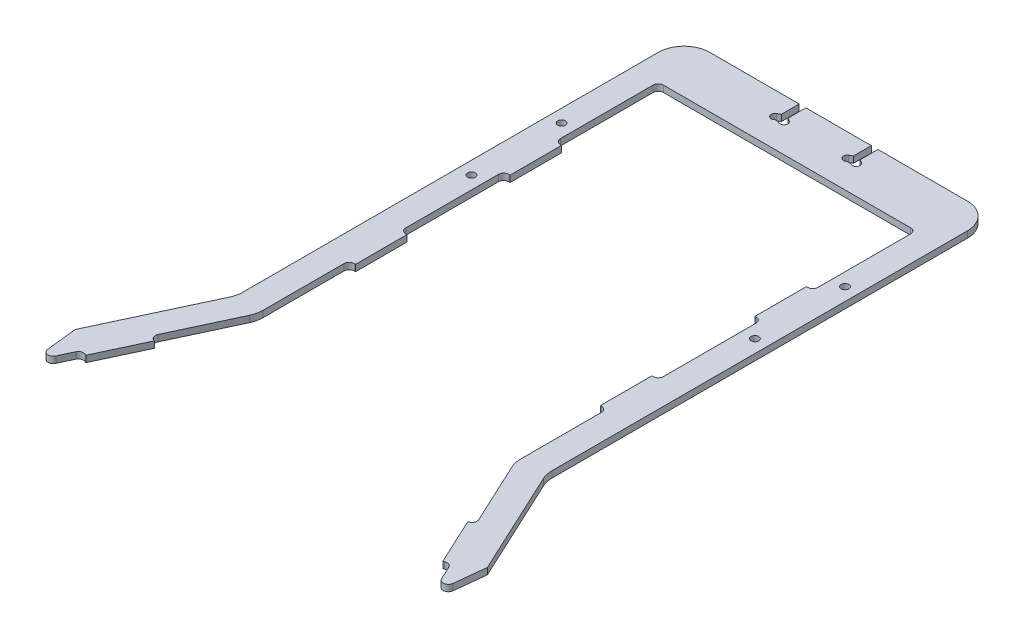
SolidWorks part; units mm, degrees
material "6061-T6 (SS)"
ref_plane "Front Plane" through (0, 0, 0) normal (0, 0, 1) x (1, 0, 0)
ref_plane "Top Plane" through (0, 0, 0) normal (0, 1, 0) x (1, 0, 0)
ref_plane "Right Plane" through (0, 0, 0) normal (1, 0, 0) x (0, 0, -1)
sketch "Sketch1" plane through (0, 0, 0) normal (0, 1, 0) x (1, 0, 0)
  line L0 (-76.2, 0) -> (76.2, 0)
  line L1 (-76.2, 0) -> (-76.2, -220.2788)
  line L3 (-63.5, -223.0943) -> (-63.5, -25.4)
  line L4 (-63.5, -25.4) -> (63.5, -25.4)
  line L5 (63.5, -25.4) -> (63.5, -223.0943)
  line L7 (76.2, -220.2788) -> (76.2, 0)
  line L8 (-76.2, -220.2788) -> (-113.1101, -299.4327)
  line L9 (-113.1101, -299.4327) -> (-101.6, -304.8)
  line L10 (-101.6, -304.8) -> (-63.5, -223.0943)
  line L11 (63.5, -223.0943) -> (101.6, -304.8)
  line L12 (76.2, -220.2788) -> (113.1101, -299.4327)
  line L13 (113.1101, -299.4327) -> (101.6, -304.8)
  point P4 (0, 0)
  dimension "D1" = 127
  dimension "D3" = 25.4
  dimension "D5" = 12.7
  dimension "D6" = 12.7
  dimension "D8" = 12.7
  dimension "D9" = 38.1
  dimension "D10" = 279.4
  dimension "D12" = 25
base flange "Base-Flange1" sketch "Sketch1" thickness 3.175 reverse thickness direction no parameters "D1"=3.175
sketch "Sketch7" plane through (0, 0, 0) normal (0, 1, 0) x (1, 0, 0)
  line L0 (-19.431, 0) -> (-19.431, -12.7)
  line L1 (76.2, 0) -> (-76.2, 0) construction
  line L2 (-19.431, -12.7) -> (-16.129, -12.7)
  line L3 (-16.129, -12.7) -> (-16.129, 0)
  line L4 (-16.129, 0) -> (-19.431, 0)
  line L9 (0, 0) -> (0, -25.4) construction
  line L10 (-63.5, -25.4) -> (63.5, -25.4) construction
  line L11 (16.129, 0) -> (19.431, 0)
  line L14 (16.129, -12.7) -> (16.129, 0)
  line L16 (19.431, -12.7) -> (16.129, -12.7)
  line L17 (19.431, 0) -> (19.431, -12.7)
  dimension "D1" = 12.7
  dimension "D2" = 3.302
  dimension "D3" = 32.258
extrude "Cut-Extrude1" cut sketch "Sketch7" against normal through all normal cut yes
sketch "Sketch12" plane through (0, 0, 0) normal (0, 1, 0) x (1, 0, 0)
  line L0 (-63.5, -223.0943) -> (-63.5, -25.4) construction
  line L1 (-63.5, -76.2) -> (-60.325, -76.2)
  line L2 (-63.5, -76.2) -> (-63.5, -101.6)
  line L3 (-63.5, -101.6) -> (-60.325, -101.6)
  line L4 (-60.325, -76.2) -> (-60.325, -101.6)
  line L5 (-80.131, -258.7596) -> (-90.8655, -281.7798)
  line L6 (-63.5, -152.4) -> (-60.325, -152.4)
  line L7 (-63.5, -152.4) -> (-63.5, -177.8)
  line L8 (-63.5, -177.8) -> (-60.325, -177.8)
  line L9 (-60.325, -152.4) -> (-60.325, -177.8)
  line L10 (-80.131, -258.7596) -> (-77.2535, -260.1014)
  line L11 (-90.8655, -281.7798) -> (-87.988, -283.1216)
  line L12 (-77.2535, -260.1014) -> (-87.988, -283.1216)
  line L13 (-101.6, -304.8) -> (-63.5, -223.0943) construction
  line L18 (-113.1101, -299.4327) -> (-101.6, -304.8) construction
  line L19 (0, 0) -> (0, -305.8108) construction
  line L24 (-63.5, -25.4) -> (63.5, -25.4) construction
  line L25 (77.2535, -260.1014) -> (87.988, -283.1216)
  line L26 (90.8655, -281.7798) -> (87.988, -283.1216)
  line L27 (80.131, -258.7596) -> (77.2535, -260.1014)
  line L28 (60.325, -152.4) -> (60.325, -177.8)
  line L29 (63.5, -177.8) -> (60.325, -177.8)
  line L30 (63.5, -152.4) -> (63.5, -177.8)
  line L31 (63.5, -152.4) -> (60.325, -152.4)
  line L32 (80.131, -258.7596) -> (90.8655, -281.7798)
  line L33 (60.325, -76.2) -> (60.325, -101.6)
  line L34 (63.5, -101.6) -> (60.325, -101.6)
  line L35 (63.5, -76.2) -> (63.5, -101.6)
  line L36 (63.5, -76.2) -> (60.325, -76.2)
  dimension "D1" = 25.4
  dimension "D2" = 3.175
  dimension "D3" = 50.8
  dimension "D4" = 50.8
  dimension "D5" = 25.4
base flange "Tab1" sketch "Sketch12" thickness 3.175 reverse thickness direction no parameters "D1"=3.175
sketch "Sketch13" plane through (0, 0, 0) normal (0, 1, 0) x (1, 0, 0)
  line L1 (-101.6, -304.8) -> (-98.9164, -299.0449)
  line L2 (-98.9164, -299.0449) -> (-101.6, -274.7492)
  line L4 (-76.2, -220.2788) -> (-113.1101, -299.4327) construction
  line L5 (-101.6, -274.7492) -> (-113.1101, -299.4327)
  line L10 (0, 0) -> (0, -299.0449) construction
  line L12 (101.6, -304.8) -> (98.9164, -299.0449)
  line L13 (113.1101, -299.4327) -> (101.6, -304.8)
  line L15 (101.6, -274.7492) -> (113.1101, -299.4327)
  line L16 (98.9164, -299.0449) -> (101.6, -274.7492)
  line L18 (-113.1101, -299.4327) -> (-101.6, -304.8)
  line L23 (-96.2327, -293.2899) -> (-101.6, -304.8) construction
  line L24 (-101.6, -304.8) -> (-90.8655, -281.7798) construction
  dimension "D1" = 24.2957
extrude "Cut-Extrude2" cut sketch "Sketch13" against normal through all normal cut yes
fillet "Fillet1" radius 2.54 14 edges at (-63.5, -1.5875, 25.4) (63.5, -1.5875, 25.4) (63.5, -1.5875, 177.8) (63.5, -1.5875, 152.4) (90.8655, -1.5875, 281.7798) (80.131, -1.5875, 258.7596) (-80.131, -1.5875, 258.7596) (-90.8655, -1.5875, 281.7798) (-63.5, -1.5875, 177.8) (-63.5, -1.5875, 152.4) (-63.5, -1.5875, 101.6) (-63.5, -1.5875, 76.2) (63.5, -1.5875, 76.2) (63.5, -1.5875, 101.6)
sketch "Sketch14" plane through (0, 0, 0) normal (0, 1, 0) x (1, 0, 0)
  line L0 (-19.431, -12.7) -> (-16.129, -12.7) construction
  line L1 (-19.431, -9.4871) -> (-18.669, -12.7) construction
  line L2 (-19.431, 0) -> (-19.431, -12.7) construction
  line L3 (-17.78, -12.7) -> (-17.78, -11.1209) construction
  line L4 (0, 0) -> (0, -4.4375) construction
  line L5 (-20.9272, -9.6631) -> (-19.431, -8.7993)
  line L6 (-19.431, -8.7993) -> (-19.431, -9.4871)
  line L7 (-16.129, -8.7993) -> (-16.129, -9.4871)
  line L8 (-14.6328, -9.6631) -> (-16.129, -8.7993)
  line L9 (19.431, -8.7993) -> (19.431, -9.4871)
  line L10 (20.9272, -9.6631) -> (19.431, -8.7993)
  line L11 (14.6328, -9.6631) -> (16.129, -8.7993)
  line L12 (16.129, -8.7993) -> (16.129, -9.4871)
  arc A0 (-20.9272, -9.6631) -> (-19.431, -9.4871) centre (-19.9747, -11.3129) ccw
  arc A5 (-14.6328, -9.6631) -> (-16.129, -9.4871) centre (-15.5853, -11.3129) cw
  arc A6 (20.9272, -9.6631) -> (19.431, -9.4871) centre (19.9747, -11.3129) cw
  arc A7 (14.6328, -9.6631) -> (16.129, -9.4871) centre (15.5853, -11.3129) ccw
  dimension "D1" = 3.81
  dimension "D2" = 3.302
  dimension "D3" = 0.762
  dimension "D4" = 30
extrude "Cut-Extrude3" cut sketch "Sketch14" against normal through all normal cut yes
fillet "Fillet2" radius 12.7 6 edges at (-76.2, -1.5875, 220.2788) (76.2, -1.5875, 220.2788) (76.2, -1.5875, 0) (-76.2, -1.5875, 0) (63.5, -1.5875, 223.0943) (-63.5, -1.5875, 223.0943)
fillet "Fillet3" radius 2.54 2 edges at (98.9164, -1.5875, 299.0449) (-98.9164, -1.5875, 299.0449)
sketch "Sketch17" plane through (0, 0, 0) normal (0, 1, 0) x (1, 0, 0)
  line L0 (63.5, -66.675) -> (76.2, -66.675) construction
  line L1 (63.5, -27.94) -> (63.5, -73.66) construction
  line L2 (76.2, -217.4632) -> (76.2, -12.7) construction
  line L4 (-60.96, -25.4) -> (60.96, -25.4) construction
  line L5 (0, 0) -> (0, 30.5399) construction
  point P0 (69.85, -66.675)
  point P2 (69.85, -111.125)
  point P27 (-69.85, -111.125)
  point P28 (-69.85, -66.675)
  dimension "D1" = 44.45
  dimension "D2" = 41.275
hole_wizard "#6 Clearance Hole1" positions "Sketch17" profile "Sketch16" hole size "#6" standard "ANSI Inch" end condition up to next
sketch "Sketch16" plane through (69.85, 0, 66.675) normal (1, 0, 0) x (0, 0, 1)
  line L0 (0, 0) -> (0, 3.175)
  line L1 (0, 3.175) -> (1.8986, 3.175)
  line L2 (1.8986, 3.175) -> (1.8986, 0)
  line L5 (1.8986, 0) -> (0, 0)
  line L11 (0, -6.35) -> (0, 107.95) construction
  dimension "Thru Hole Dia." = 3.7973
  dimension "Thru Hole Depth" = 3.175
sketch "Bend-Lines1" [suppressed] plane through (0, 0, 0) normal (0, 1, 0) x (1, 0, 0)
sketch "Bounding-Box1" [suppressed] plane through (0, 0, 0) normal (0, 1, 0) x (1, 0, 0)
sheet metal parameters "Sheet-Metal1" thickness 3.175 parameters "D1"=3.175
flat pattern "Flat-Pattern1" [suppressed]
sketch "Bend-Lines2" plane through (0, 0, 0) normal (0, 1, 0) x (1, 0, 0)
sketch3d "Bounding-Box2" [suppressed]
  line L0 (-150.221, -355.6, 0) -> (-150.221, 0, 0) construction
  line L1 (150.221, -355.6, 0) -> (150.221, 0, 0) construction
  line L2 (-150.221, -355.6, 0) -> (150.221, -355.6, 0) construction
  line L3 (-150.221, 0, 0) -> (150.221, 0, 0) construction
sheet metal parameters "Sheet-Metal2" thickness 3.175 parameters "D1"=3.175
flat pattern "Flat-Pattern1"
sketch "Bend-Lines2" plane through (0, 0, 0) normal (0, 1, 0) x (1, 0, 0)
sketch3d "Bounding-Box2" [suppressed]
  line L0 (-125.2985, -304.8, 0) -> (-125.2985, 0, 0) construction
  line L1 (125.2985, -304.8, 0) -> (125.2985, 0, 0) construction
  line L2 (-125.2985, -304.8, 0) -> (125.2985, -304.8, 0) construction
  line L3 (-125.2985, 0, 0) -> (125.2985, 0, 0) construction
sheet metal parameters "Sheet-Metal3" thickness 3.175 parameters "D1"=3.175
flat pattern "Flat-Pattern3"
sketch "Bend-Lines3" plane through (0, 0, 0) normal (0, 1, 0) x (1, 0, 0)
sketch3d "Bounding-Box3" [suppressed]
  line L0 (126.0258, -302.871, 0) -> (73.6666, 15.3992, 0) construction
  line L1 (28.3517, -318.9395, 0) -> (-24.0075, -0.6693, 0) construction
  line L2 (126.0258, -302.871, 0) -> (28.3517, -318.9395, 0) construction
  line L3 (73.6666, 15.3992, 0) -> (-24.0075, -0.6693, 0) construction
sheet metal parameters "Sheet-Metal4" thickness 3.175 parameters "D1"=3.175
flat pattern "Flat-Pattern4"
sketch "Bend-Lines4" plane through (0, 0, 0) normal (0, 1, 0) x (1, 0, 0)
sketch3d "Bounding-Box4" [suppressed]
  line L0 (-126.0258, -302.871, 0) -> (-74.8011, 8.5031, 0) construction
  line L1 (-70.2702, -312.0434, 0) -> (-19.0455, -0.6693, 0) construction
  line L2 (-126.0258, -302.871, 0) -> (-70.2702, -312.0434, 0) construction
  line L3 (-74.8011, 8.5031, 0) -> (-19.0455, -0.6693, 0) construction
sheet metal parameters "Sheet-Metal5" thickness 3.175 parameters "D1"=3.175
flat pattern "Flat-Pattern5"
sketch "Bend-Lines5" plane through (0, 0, 0) normal (0, 1, 0) x (1, 0, 0)
sketch3d "Bounding-Box5" [suppressed]
  line L0 (-113.1101, -304.8, 0) -> (-113.1101, 0, 0) construction
  line L1 (113.1101, -304.8, 0) -> (113.1101, 0, 0) construction
  line L2 (-113.1101, -304.8, 0) -> (113.1101, -304.8, 0) construction
  line L3 (-113.1101, 0, 0) -> (113.1101, 0, 0) construction
sheet metal parameters "Sheet-Metal6" thickness 3.175 parameters "D1"=3.175
flat pattern "Flat-Pattern5"
sketch "Bend-Lines5" plane through (0, 0, 0) normal (0, 1, 0) x (1, 0, 0)
sketch3d "Bounding-Box5" [suppressed]
  line L0 (104.4775, -303.9645, 0) -> (104.4775, 0, 0) construction
  line L1 (-104.4775, -303.9645, 0) -> (-104.4776, 0, 0) construction
  line L2 (104.4775, -303.9645, 0) -> (-104.4775, -303.9645, 0) construction
  line L3 (104.4775, 0, 0) -> (-104.4776, 0, 0) construction
sheet metal parameters "Sheet-Metal7" thickness 3.175 parameters "D1"=3.175
flat pattern "Flat-Pattern5"
sketch "Bend-Lines5" plane through (0, 0, 0) normal (0, 1, 0) x (1, 0, 0)
sketch3d "Bounding-Box5" [suppressed]
  line L0 (101.6, -292.2951, 0) -> (101.5999, 0, 0) construction
  line L1 (-101.6, -292.2951, 0) -> (-101.6001, 0, 0) construction
  line L2 (101.6, -292.2951, 0) -> (-101.6, -292.2951, 0) construction
  line L3 (101.5999, 0, 0) -> (-101.6001, 0, 0) construction
sheet metal parameters "Sheet-Metal8" thickness 3.175 parameters "D1"=3.175
flat pattern "Flat-Pattern5"
sketch "Bend-Lines5" plane through (0, 0, 0) normal (0, 1, 0) x (1, 0, 0)
sketch3d "Bounding-Box5" [suppressed]
  line L0 (101.6, -292.2951, 0) -> (101.5999, 0, 0) construction
  line L1 (-101.6, -292.2951, 0) -> (-101.6001, 0, 0) construction
  line L2 (101.6, -292.2951, 0) -> (-101.6, -292.2951, 0) construction
  line L3 (101.5999, 0, 0) -> (-101.6001, 0, 0) construction
